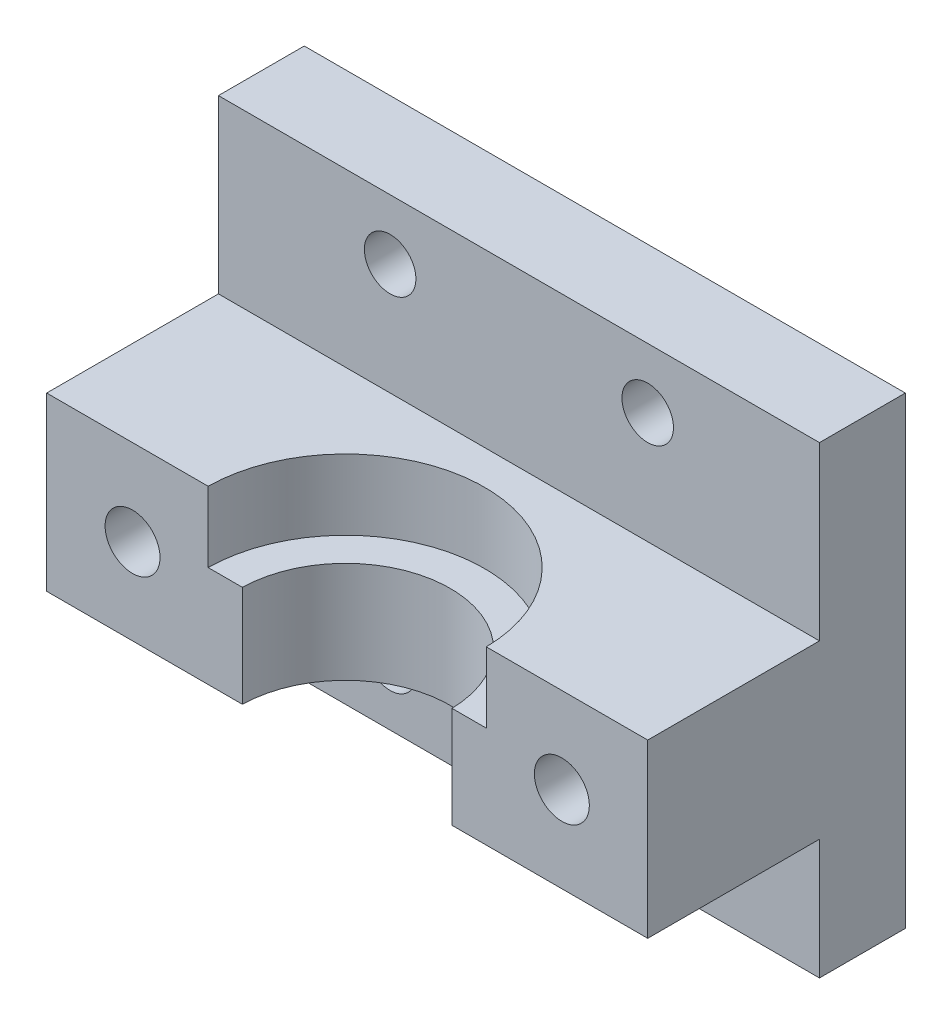
SolidWorks part; units mm, degrees
ref_plane "Front Plane" through (0, 0, 0) normal (0, 0, 1) x (1, 0, 0)
ref_plane "Top Plane" through (0, 0, 0) normal (0, 1, 0) x (1, 0, 0)
ref_plane "Right Plane" through (0, 0, 0) normal (1, 0, 0) x (0, 0, -1)
sketch "Sketch1" plane through (0, 0, 0) normal (0, 0, 1) x (1, 0, 0)
  line L1 (0, 0) -> (35, 0)
  line L2 (0, 0) -> (0, -27)
  line L3 (0, -27) -> (35, -27)
  line L4 (35, 0) -> (35, -27)
  circle A0 centre (10, -3.5) radius 1.5
  circle A1 centre (25, -3.5) radius 1.5
  circle A2 centre (10, -23.5) radius 1.5
  circle A3 centre (25, -23.5) radius 1.5
  dimension "D3" = 3
  dimension "D4" = 3
  dimension "D5" = 3
  dimension "D6" = 3
  dimension "D1" = 27
  dimension "D2" = 35
  dimension "D7" = 3.5
  dimension "D8" = 3.5
  dimension "D9" = 3.5
  dimension "D10" = 3.5
  dimension "D11" = 10
  dimension "D12" = 10
  dimension "D13" = 10
  dimension "D14" = 10
extrude "Boss-Extrude1" add sketch "Sketch1" along normal blind 25
sketch "Sketch3" plane through (0, 0, 0) normal (-1, 0, 0) x (0, 0, 1)
  line L1 (25, 0) -> (5, 0)
  line L2 (25, 0) -> (25, -10)
  line L3 (25, -10) -> (5, -10)
  line L4 (5, 0) -> (5, -10)
  line L5 (25, -27) -> (5, -27)
  line L6 (25, -27) -> (25, -20)
  line L7 (25, -20) -> (5, -20)
  line L8 (5, -27) -> (5, -20)
  dimension "D1" = 10
  dimension "D2" = 20
  dimension "D3" = 7
  dimension "D4" = 20
extrude "Cut-Extrude1" cut sketch "Sketch3" against normal through all
sketch "Sketch4" plane through (0, -10, 0) normal (0, 1, 0) x (1, 0, 0)
  line L6 (35, -5) -> (0, -5) construction
  line L7 (0, -5) -> (0, -25) construction
  circle A0 centre (17.4997, -15.1) radius 6.1
  point P6 (0, -15)
  dimension "D1" = 12.2
  dimension "D2" = 4
  dimension "D3" = 17.5
extrude "Cut-Extrude6" cut sketch "Sketch4" against normal through all
sketch "Sketch5" plane through (0, -10, 0) normal (0, 1, 0) x (1, 0, 0)
  circle A0 centre (17.4997, -15.1) radius 8.1
  dimension "D1" = 16.2
extrude "Cut-Extrude7" cut sketch "Sketch5" against normal blind 4.1
sketch "Sketch7" plane through (0, 0, 25) normal (0, 0, 1) x (1, 0, 0)
  line L0 (35, -10) -> (0, -10) construction
  line L1 (35, -10) -> (0, -10) construction
  line L2 (0, -10) -> (0, -20) construction
  line L3 (35, -20) -> (35, -10) construction
  circle A0 centre (5, -15) radius 1.6
  circle A1 centre (30, -15) radius 1.6
  dimension "D1" = 3.2
  dimension "D2" = 3.2
  dimension "D3" = 5
  dimension "D4" = 5
  dimension "D5" = 5
  dimension "D6" = 5
extrude "Cut-Extrude8" cut sketch "Sketch7" against normal through all
sketch "Sketch9" plane through (0, 0, 0) normal (0, 0, -1) x (-1, 0, 0)
  line L1 (-30, -11.95) -> (-32.6414, -13.475)
  line L2 (-32.6414, -13.475) -> (-32.6414, -16.525)
  line L3 (-32.6414, -16.525) -> (-30, -18.05)
  line L4 (-30, -18.05) -> (-27.3586, -16.525)
  line L5 (-27.3586, -16.525) -> (-27.3586, -13.475)
  line L6 (-27.3586, -13.475) -> (-30, -11.95)
  line L7 (-5, -11.95) -> (-7.6414, -13.475)
  line L8 (-7.6414, -13.475) -> (-7.6414, -16.525)
  line L9 (-7.6414, -16.525) -> (-5, -18.05)
  line L10 (-5, -18.05) -> (-2.3586, -16.525)
  line L11 (-2.3586, -16.525) -> (-2.3586, -13.475)
  line L12 (-2.3586, -13.475) -> (-5, -11.95)
  circle A0 centre (-30, -15) radius 2.6414 construction
  circle A1 centre (-5, -15) radius 2.6414 construction
  dimension "D1" = 6.1
  dimension "D2" = 6.1
extrude "Cut-Extrude9" cut sketch "Sketch9" against normal blind 10
sketch "Sketch10" plane through (0, 0, 25) normal (0, 0, 1) x (1, 0, 0)
  line L1 (0, -10) -> (35, -10)
  line L2 (0, -10) -> (0, -20)
  line L3 (0, -20) -> (35, -20)
  line L4 (35, -10) -> (35, -20)
extrude "Cut-Extrude10" cut sketch "Sketch10" against normal blind 10
